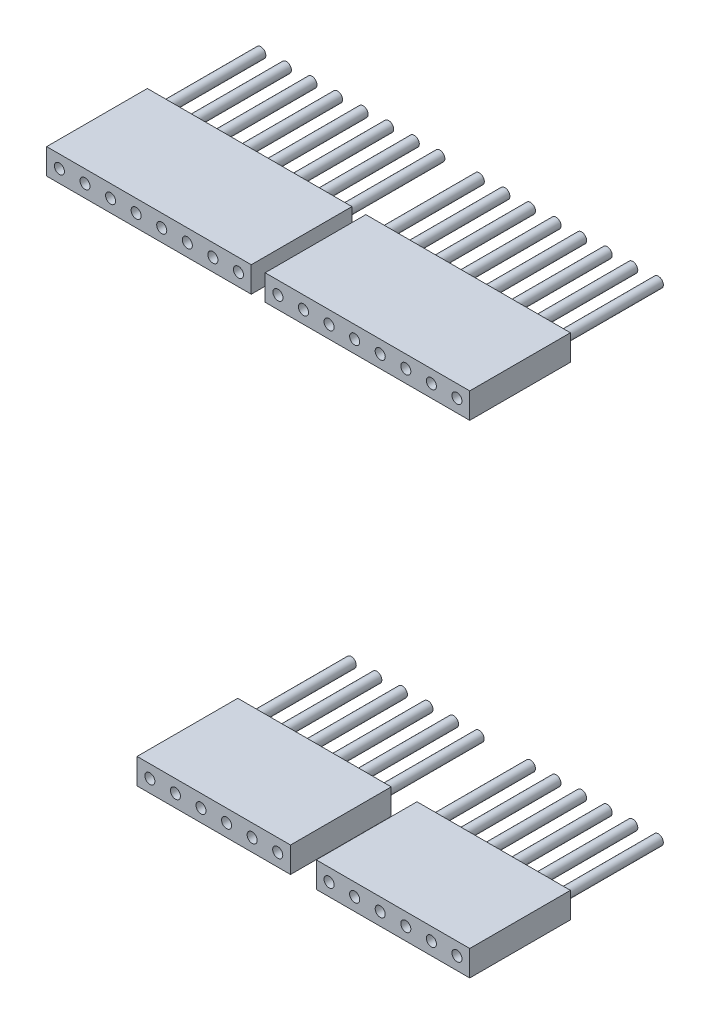
SolidWorks part; units mm, degrees
ref_plane "Front Plane" through (0, 0, 0) normal (0, 0, 1) x (1, 0, 0)
ref_plane "Top Plane" through (0, 0, 0) normal (0, 1, 0) x (1, 0, 0)
ref_plane "Right Plane" through (0, 0, 0) normal (1, 0, 0) x (0, 0, -1)
sketch "Sketch1" plane through (0, 0, 0) normal (0, 0, 1) x (1, 0, 0)
  line L0 (21.75, 50.5) -> (42.07, 50.5) construction
  line L1 (30.73, 1.27) -> (45.97, 1.27)
  line L2 (30.73, 1.27) -> (30.73, 3.81)
  line L3 (30.73, 3.81) -> (45.97, 3.81)
  line L4 (45.97, 1.27) -> (45.97, 3.81)
  line L5 (48.53, 1.27) -> (63.77, 1.27)
  line L6 (48.53, 1.27) -> (48.53, 3.81)
  line L7 (48.53, 3.81) -> (63.77, 3.81)
  line L8 (63.77, 1.27) -> (63.77, 3.81)
  line L9 (21.75, 49.23) -> (42.07, 49.23)
  line L10 (21.75, 49.23) -> (21.75, 51.77)
  line L11 (21.75, 51.77) -> (42.07, 51.77)
  line L12 (42.07, 49.23) -> (42.07, 51.77)
  line L13 (43.45, 49.23) -> (63.77, 49.23)
  line L14 (43.45, 49.23) -> (43.45, 51.77)
  line L15 (43.45, 51.77) -> (63.77, 51.77)
  line L16 (63.77, 49.23) -> (63.77, 51.77)
  circle A0 centre (23.02, 50.5) radius 0.5
  circle A1 centre (25.56, 50.5) radius 0.5
  circle A2 centre (28.1, 50.5) radius 0.5
  circle A3 centre (30.64, 50.5) radius 0.5
  circle A4 centre (33.18, 50.5) radius 0.5
  circle A5 centre (35.72, 50.5) radius 0.5
  circle A6 centre (38.26, 50.5) radius 0.5
  circle A7 centre (40.8, 50.5) radius 0.5
  circle A8 centre (44.72, 50.5) radius 0.5
  circle A9 centre (32, 2.54) radius 0.5
  circle A10 centre (49.8, 2.54) radius 0.5
  circle A11 centre (47.26, 50.5) radius 0.5
  circle A12 centre (49.8, 50.5) radius 0.5
  circle A13 centre (52.34, 50.5) radius 0.5
  circle A14 centre (54.88, 50.5) radius 0.5
  circle A15 centre (57.42, 50.5) radius 0.5
  circle A16 centre (59.96, 50.5) radius 0.5
  circle A17 centre (62.5, 50.5) radius 0.5
  circle A18 centre (34.54, 2.54) radius 0.5
  circle A19 centre (52.34, 2.54) radius 0.5
  circle A20 centre (37.08, 2.54) radius 0.5
  circle A21 centre (54.88, 2.54) radius 0.5
  circle A22 centre (39.62, 2.54) radius 0.5
  circle A23 centre (57.42, 2.54) radius 0.5
  circle A24 centre (42.16, 2.54) radius 0.5
  circle A25 centre (59.96, 2.54) radius 0.5
  circle A26 centre (44.7, 2.54) radius 0.5
  circle A27 centre (62.5, 2.54) radius 0.5
  point P20 (30.73, 2.54)
  point P43 (48.53, 2.54)
  dimension "D3" = 20.32
  dimension "D4" = 1.38
  dimension "D5" = 2.56
  dimension "D6" = 45.42
  dimension "D8" = 1.27
  dimension "D15" = 1
  dimension "D16" = 1
  dimension "D17" = 1
  dimension "D18" = 1
  dimension "D1" = 2.54
  dimension "D2" = 2.54
  dimension "D7" = 15.24
  dimension "D9" = 8
  dimension "D10" = 1.27
  dimension "D11" = 1.27
  dimension "D12" = 1.27
  dimension "D13" = 8
  dimension "D14" = 6
extrude "Boss-Extrude1" add sketch "Sketch1" along normal blind 10
extrude "Boss-Extrude2" add sketch "Sketch1<3>" against normal blind 10 separate body contours A2 | A6 | A7 | A5 | A4 | A3 | A1 | A0 | A8 | A11 | A12 | A13 | A14 | A15 | A16 | A17 | A10 | A19 | A21 | A23 | A27 | A26 | A24 | A22 | A20 | A18 | A9 | A25
sketch "Sketch1<3>" plane through (0, 0, 0) normal (0, 0, 1) x (1, 0, 0) same geometry as "Sketch1"
